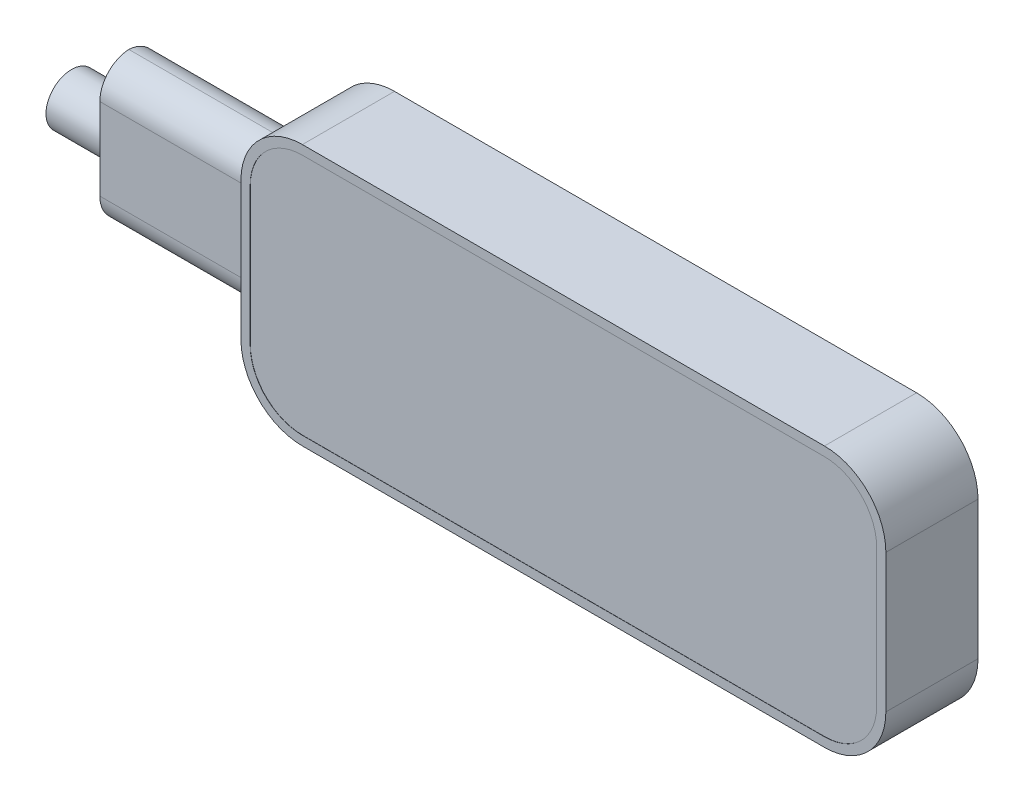
SolidWorks part; units mm, degrees
material "3003-H16"
ref_plane "Front Plane" through (0, 0, 0) normal (0, 0, 1) x (1, 0, 0)
ref_plane "Top Plane" through (0, 0, 0) normal (0, 1, 0) x (1, 0, 0)
ref_plane "Right Plane" through (0, 0, 0) normal (1, 0, 0) x (0, 0, -1)
sketch "Sketch2" plane through (0, 0, 0) normal (0, 0, 1) x (1, 0, 0)
  line L1 (40.005, 16.1925) -> (-40.005, 16.1925)
  line L2 (40.005, 16.1925) -> (40.005, -16.1925)
  line L3 (40.005, -16.1925) -> (-40.005, -16.1925)
  line L4 (-40.005, 16.1925) -> (-40.005, -16.1925)
  line L5 (40.005, 16.1925) -> (-40.005, -16.1925) construction
  line L6 (40.005, -16.1925) -> (-40.005, 16.1925) construction
  point P0 (0, 0)
  dimension "D1" = 80.01
  dimension "D2" = 32.385
extrude "Boss-Extrude1" add sketch "Sketch2" along normal blind 11.43
fillet "Fillet1" radius 7.62 4 edges at (-40.005, -16.1925, 5.715) (40.005, -16.1925, 5.715) (40.005, 16.1925, 5.715) (-40.005, 16.1925, 5.715)
sketch "Sketch4" plane through (0, 0, 11.43) normal (0, 0, 1) x (1, 0, 0)
  line L8 (-38.862, 8.5725) -> (-38.862, -8.5725)
  line L9 (-32.385, -15.0495) -> (32.385, -15.0495)
  line L10 (38.862, -8.5725) -> (38.862, 8.5725)
  line L11 (32.385, 15.0495) -> (-32.385, 15.0495)
  line L12 (-38.862, 8.5725) -> (-38.862, -8.5725)
  line L13 (-32.385, -15.0495) -> (32.385, -15.0495)
  line L14 (38.862, -8.5725) -> (38.862, 8.5725)
  line L15 (32.385, 15.0495) -> (-32.385, 15.0495)
  arc A8 (-38.862, -8.5725) -> (-32.385, -15.0495) centre (-32.385, -8.5725) ccw
  arc A9 (32.385, -15.0495) -> (38.862, -8.5725) centre (32.385, -8.5725) ccw
  arc A10 (38.862, 8.5725) -> (32.385, 15.0495) centre (32.385, 8.5725) ccw
  arc A11 (-32.385, 15.0495) -> (-38.862, 8.5725) centre (-32.385, 8.5725) ccw
  arc A12 (-38.862, -8.5725) -> (-32.385, -15.0495) centre (-32.385, -8.5725) ccw
  arc A13 (32.385, -15.0495) -> (38.862, -8.5725) centre (32.385, -8.5725) ccw
  arc A14 (38.862, 8.5725) -> (32.385, 15.0495) centre (32.385, 8.5725) ccw
  arc A15 (-32.385, 15.0495) -> (-38.862, 8.5725) centre (-32.385, 8.5725) ccw
  dimension "D1" = 1.143
extrude "Cut-Extrude1" cut sketch "Sketch4" against normal blind 0.0254
sketch "Sketch5" plane through (-40.005, 0, 0) normal (-1, 0, 0) x (0, 0, 1)
  line L0 (0, 0) -> (11.43, 0) construction
  line L1 (2.5636, 6.731) -> (5.7386, 6.731)
  line L2 (2.5636, 6.731) -> (2.5636, -6.731)
  line L3 (2.5636, -6.731) -> (5.7386, -6.731)
  line L4 (5.7386, 6.731) -> (5.7386, -6.731)
  line L5 (2.5636, 6.731) -> (5.7386, -6.731) construction
  line L6 (2.5636, -6.731) -> (5.7386, 6.731) construction
  line L7 (0, 8.5725) -> (0, -8.5725) construction
  line L8 (11.43, 8.5725) -> (11.43, -8.5725) construction
  point P0 (4.1511, 0)
  dimension "D1" = 3.175
  dimension "D2" = 13.462
extrude "Cut-Extrude2" cut sketch "Sketch5" against normal blind 5.08
sketch "Sketch6" plane through (-40.005, 0, 0) normal (-1, 0, 0) x (0, 0, 1)
  line L0 (0, 0) -> (11.1217, 0) construction
  line L1 (1.0725, 8.89) -> (8.2607, 8.89)
  line L2 (1.0725, 8.89) -> (1.0725, -8.89)
  line L3 (1.0725, -8.89) -> (8.2607, -8.89)
  line L4 (8.2607, 8.89) -> (8.2607, -8.89)
  line L5 (1.0725, 8.89) -> (8.2607, -8.89) construction
  line L6 (1.0725, -8.89) -> (8.2607, 8.89) construction
  line L7 (0, 8.5725) -> (0, -8.5725) construction
  point P0 (4.6666, 0)
  dimension "D1" = 7.1882
  dimension "D2" = 17.78
extrude "Boss-Extrude2" add sketch "Sketch6" along normal blind 20.6502 from offset 0.0254 separate body
fillet "Fillet2" radius 3.81 4 edges at (-50.3555, -8.89, 1.0725) (-50.3555, -8.89, 8.2607) (-50.3555, 8.89, 1.0725) (-50.3555, 8.89, 8.2607)
sketch "Sketch7" plane through (-60.6806, 0, 0) normal (-1, 0, 0) x (0, 0, 1)
  circle A0 centre (4.6537, 0) radius 3.175
  dimension "D1" = 6.35
extrude "Boss-Extrude3" add sketch "Sketch7" along normal blind 7.112
sketch "Sketch8" plane through (0, 0, 0) normal (0, 0, -1) x (-1, 0, 0)
  line L0 (40.0304, -8.8839) -> (60.6806, -8.8839) construction
  line L1 (60.6806, 8.8839) -> (40.0304, 8.8839) construction
  line L2 (40.0304, -8.8839) -> (60.6806, -8.8839)
  line L3 (60.6806, 8.8839) -> (40.0304, 8.8839)
  line L4 (-32.385, -16.1925) -> (32.385, -16.1925)
  line L5 (40.005, -8.5725) -> (40.005, 8.5725)
  line L6 (32.385, 16.1925) -> (-32.385, 16.1925)
  line L7 (-40.005, 8.5725) -> (-40.005, -8.5725)
  line L8 (-32.385, -16.1925) -> (32.385, -16.1925)
  line L9 (40.005, -8.5725) -> (40.005, 8.5725)
  line L10 (32.385, 16.1925) -> (-32.385, 16.1925)
  line L11 (-40.005, 8.5725) -> (-40.005, -8.5725)
  arc A4 (32.385, -16.1925) -> (40.005, -8.5725) centre (32.385, -8.5725) ccw
  arc A5 (40.005, 8.5725) -> (32.385, 16.1925) centre (32.385, 8.5725) ccw
  arc A6 (-32.385, 16.1925) -> (-40.005, 8.5725) centre (-32.385, 8.5725) ccw
  arc A7 (-40.005, -8.5725) -> (-32.385, -16.1925) centre (-32.385, -8.5725) ccw
  arc A8 (32.385, -16.1925) -> (40.005, -8.5725) centre (32.385, -8.5725) ccw
  arc A9 (40.005, 8.5725) -> (32.385, 16.1925) centre (32.385, 8.5725) ccw
  arc A10 (-32.385, 16.1925) -> (-40.005, 8.5725) centre (-32.385, 8.5725) ccw
  arc A11 (-40.005, -8.5725) -> (-32.385, -16.1925) centre (-32.385, -8.5725) ccw
  dimension "D1" = 0
